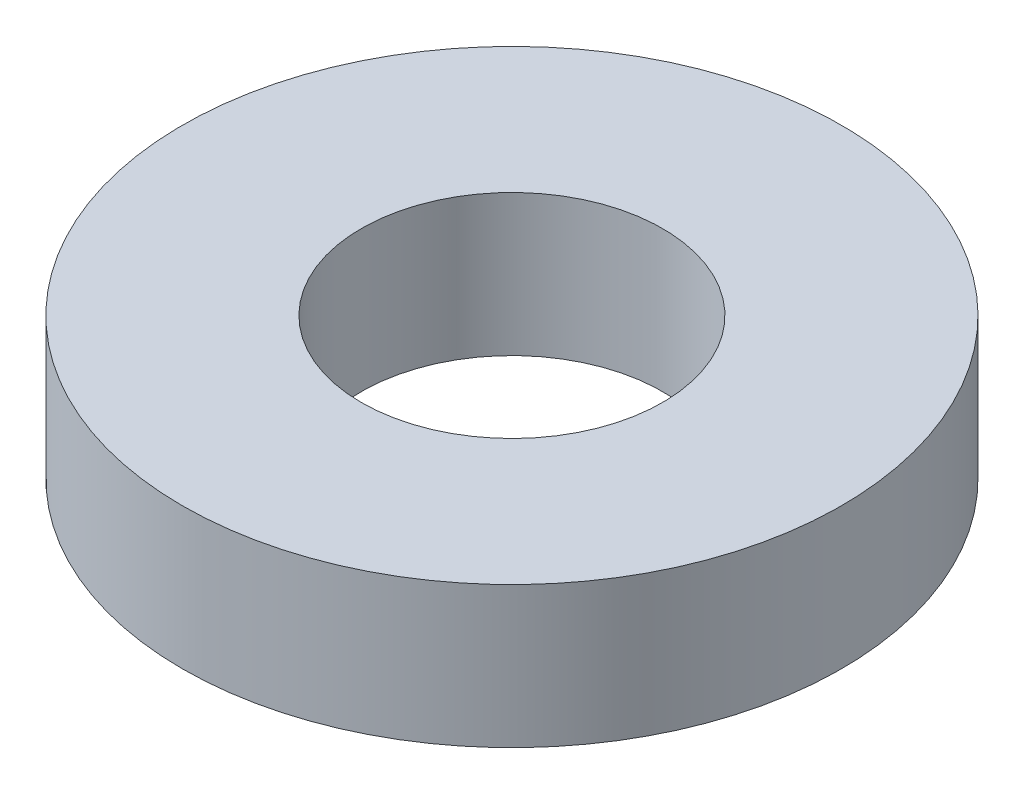
SolidWorks part; units mm, degrees
ref_plane "Front Plane" through (0, 0, 0) normal (0, 0, 1) x (1, 0, 0)
ref_plane "Top Plane" through (0, 0, 0) normal (0, 1, 0) x (1, 0, 0)
ref_plane "Right Plane" through (0, 0, 0) normal (1, 0, 0) x (0, 0, -1)
sketch "Sketch1" plane through (0, 0, 0) normal (0, 1, 0) x (1, 0, 0)
  circle A0 centre (0, 0) radius 1.6
  circle A1 centre (0, 0) radius 3.5
  dimension "D1" = 3.2
  dimension "D2" = 7
extrude "Boss-Extrude1" add sketch "Sketch1" along normal blind 1.5
